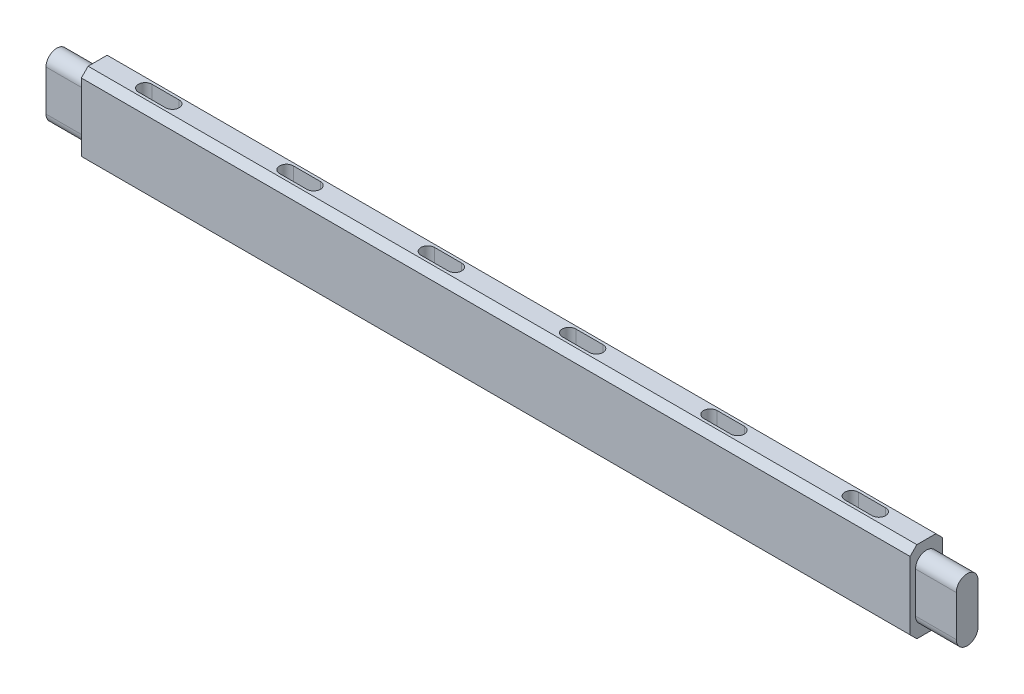
SolidWorks part; units mm, degrees
ref_plane "Front" through (0, 0, 0) normal (0, 0, 1) x (1, 0, 0)
ref_plane "Top" through (0, 0, 0) normal (0, 1, 0) x (1, 0, 0)
ref_plane "Right" through (0, 0, 0) normal (1, 0, 0) x (0, 0, -1)
sketch "Esquisse1" plane through (0, 0, 0) normal (0, 0, 1) x (1, 0, 0)
  line L1 (0, 0) -> (610, 0)
  line L2 (0, 0) -> (0, 60)
  line L3 (0, 60) -> (610, 60)
  line L4 (610, 0) -> (610, 60)
  dimension "D1" = 610
  dimension "D2" = 60
extrude "Boss.-Extru.1" add sketch "Esquisse1" along normal blind 24
sketch "Esquisse2" plane through (0, 0, 0) normal (-1, 0, 0) x (0, 0, 1)
  line L0 (12, 0) -> (12, 60) construction
  line L1 (24, 0) -> (0, 0) construction
  line L2 (24, 60) -> (0, 60) construction
  line L3 (12, 15) -> (12, 45) construction
  line L4 (4, 15) -> (4, 45)
  line L5 (20, 15) -> (20, 45)
  arc A0 (4, 15) -> (20, 15) centre (12, 15) ccw
  arc A1 (20, 45) -> (4, 45) centre (12, 45) ccw
  point P8 (12, 30)
  dimension "D1" = 16
  dimension "D2" = 30
extrude "Boss.-Extru.2" add sketch "Esquisse2" along normal blind 30
extrude "Boss.-Extru.3" add sketch "Esquisse2<2>" against normal blind 30 from vertex starting at point (610, 60, 0)
sketch "Esquisse2<2>" plane through (0, 0, 0) normal (-1, 0, 0) x (0, 0, 1) same geometry as "Esquisse2"
chamfer "Chanfrein1" distance 5 angle 45 4 edges at (305, 0, 24) (305, 0, 0) (305, 60, 0) (305, 60, 24)
sketch "Esquisse3" [suppressed] plane through (0, 80, 0) normal (0, 1, 0) x (1, 0, 0)
  line L0 (305, -27) -> (305, -5) construction
  line L1 (0, -27) -> (610, -27) construction
  line L2 (305, -16) -> (415, -16) construction
  line L3 (360, -16) -> (360, -5) construction
  line L4 (610, -5) -> (0, -5) construction
  line L7 (305, -16) -> (195, -16) construction
  line L8 (185, -16) -> (205, -16) construction
  line L9 (185, -11) -> (205, -11)
  line L10 (185, -21) -> (205, -21)
  line L11 (82, -16) -> (102, -16) construction
  line L12 (82, -11) -> (102, -11)
  line L13 (82, -21) -> (102, -21)
  line L14 (-21, -16) -> (-1, -16) construction
  line L15 (-21, -11) -> (-1, -11)
  line L16 (-21, -21) -> (-1, -21)
  line L17 (-124, -16) -> (-104, -16) construction
  line L18 (-124, -11) -> (-104, -11)
  line L19 (-124, -21) -> (-104, -21)
  line L20 (-227, -16) -> (-207, -16) construction
  line L21 (-227, -11) -> (-207, -11)
  line L22 (-227, -21) -> (-207, -21)
  line L23 (595, -16) -> (315, -16) construction
  line L24 (595, -16) -> (315, -16) construction
  line L25 (295, -16) -> (315, -16) construction
  line L26 (295, -11) -> (315, -11)
  line L27 (295, -21) -> (315, -21)
  line L29 (837, -16) -> (817, -16) construction
  line L30 (837, -11) -> (817, -11)
  line L31 (837, -21) -> (817, -21)
  line L32 (734, -16) -> (714, -16) construction
  line L33 (734, -11) -> (714, -11)
  line L34 (734, -21) -> (714, -21)
  line L35 (631, -16) -> (611, -16) construction
  line L36 (631, -11) -> (611, -11)
  line L37 (631, -21) -> (611, -21)
  line L38 (528, -16) -> (508, -16) construction
  line L39 (528, -11) -> (508, -11)
  line L40 (528, -21) -> (508, -21)
  line L41 (425, -16) -> (405, -16) construction
  line L42 (425, -11) -> (405, -11)
  line L43 (425, -21) -> (405, -21)
  line L89 (-65, -16) -> (-45, -16) construction
  line L90 (-65, -11) -> (-45, -11)
  line L91 (-65, -21) -> (-45, -21)
  line L92 (-330, -16) -> (-310, -16) construction
  line L93 (-330, -11) -> (-310, -11)
  line L94 (-330, -21) -> (-310, -21)
  arc A0 (185, -11) -> (185, -21) centre (185, -16) ccw
  arc A1 (205, -21) -> (205, -11) centre (205, -16) ccw
  arc A2 (82, -11) -> (82, -21) centre (82, -16) ccw
  arc A3 (102, -21) -> (102, -11) centre (102, -16) ccw
  arc A4 (-21, -11) -> (-21, -21) centre (-21, -16) ccw
  arc A5 (-1, -21) -> (-1, -11) centre (-1, -16) ccw
  arc A6 (-124, -11) -> (-124, -21) centre (-124, -16) ccw
  arc A7 (-104, -21) -> (-104, -11) centre (-104, -16) ccw
  arc A8 (-227, -11) -> (-227, -21) centre (-227, -16) ccw
  arc A9 (-207, -21) -> (-207, -11) centre (-207, -16) ccw
  arc A10 (295, -11) -> (295, -21) centre (295, -16) ccw
  arc A11 (315, -21) -> (315, -11) centre (315, -16) ccw
  arc A14 (837, -11) -> (837, -21) centre (837, -16) cw
  arc A15 (817, -21) -> (817, -11) centre (817, -16) cw
  arc A16 (734, -11) -> (734, -21) centre (734, -16) cw
  arc A17 (714, -21) -> (714, -11) centre (714, -16) cw
  arc A18 (631, -11) -> (631, -21) centre (631, -16) cw
  arc A19 (611, -21) -> (611, -11) centre (611, -16) cw
  arc A20 (528, -11) -> (528, -21) centre (528, -16) cw
  arc A21 (508, -21) -> (508, -11) centre (508, -16) cw
  arc A22 (425, -11) -> (425, -21) centre (425, -16) cw
  arc A23 (405, -21) -> (405, -11) centre (405, -16) cw
  arc A56 (-330, -11) -> (-330, -21) centre (-330, -16) ccw
  arc A57 (-310, -21) -> (-310, -11) centre (-310, -16) ccw
  point P10 (195, -16)
  point P19 (92, -16)
  point P26 (-11, -16)
  point P33 (-114, -16)
  point P40 (-217, -16)
  point P49 (305, -16)
  point P59 (827, -16)
  point P66 (724, -16)
  point P73 (621, -16)
  point P80 (518, -16)
  point P87 (415, -16)
  point P94 (-11, -16)
  point P104 (-11, -16)
  point P111 (-11, -16)
  point P118 (-11, -16)
  point P125 (-16, -16)
  point P132 (-16, -16)
  point P139 (-16, -16)
  point P146 (-16, -16)
  point P153 (-55, -16)
  point P160 (-55, -16)
  point P167 (-55, -16)
  point P174 (-55, -16)
  point P181 (-55, -16)
  point P188 (-55, -16)
  point P195 (-55, -16)
  point P202 (-55, -16)
  point P209 (-320, -16)
  dimension "D1" = 10
  dimension "D2" = 208
  dimension "D3" = 20
  dimension "D4" = 6
  dimension "D5" = 104
extrude "Enlèv. mat.-Extru.1" [suppressed] cut sketch "Esquisse3" against normal blind 15
sketch "Esquisse5" plane through (0, 60, 0) normal (0, 1, 0) x (1, 0, 0)
  line L0 (253, -27.4919) -> (253, 3.4919) construction
  line L1 (0, 0) -> (610, 0) construction
  line L2 (253, -12) -> (357, -12) construction
  line L3 (305, -12) -> (305, -5) construction
  line L5 (610, -5) -> (0, -5) construction
  line L7 (253, -12) -> (149, -12) construction
  line L8 (139, -12) -> (159, -12) construction
  line L9 (139, -7) -> (159, -7)
  line L10 (139, -17) -> (159, -17)
  line L11 (35, -12) -> (55, -12) construction
  line L12 (35, -7) -> (55, -7)
  line L13 (35, -17) -> (55, -17)
  line L23 (389.8909, -12) -> (263, -12) construction
  line L24 (389.8909, -12) -> (263, -12) construction
  line L25 (243, -12) -> (263, -12) construction
  line L26 (243, -7) -> (263, -7)
  line L27 (243, -17) -> (263, -17)
  line L35 (575, -12) -> (555, -12) construction
  line L36 (575, -7) -> (555, -7)
  line L37 (575, -17) -> (555, -17)
  line L38 (471, -12) -> (451, -12) construction
  line L39 (471, -7) -> (451, -7)
  line L40 (471, -17) -> (451, -17)
  line L41 (367, -12) -> (347, -12) construction
  line L42 (367, -7) -> (347, -7)
  line L43 (367, -17) -> (347, -17)
  line L341 (-69, -12) -> (-49, -12) construction
  line L342 (-69, -7) -> (-49, -7)
  line L343 (-69, -17) -> (-49, -17)
  line L344 (-173, -12) -> (-153, -12) construction
  line L345 (-173, -7) -> (-153, -7)
  line L346 (-173, -17) -> (-153, -17)
  line L347 (-277, -12) -> (-257, -12) construction
  line L348 (-277, -7) -> (-257, -7)
  line L349 (-277, -17) -> (-257, -17)
  line L350 (-381, -12) -> (-361, -12) construction
  line L351 (-381, -7) -> (-361, -7)
  line L352 (-381, -17) -> (-361, -17)
  line L353 (-69, -12) -> (-49, -12) construction
  line L354 (-69, -7) -> (-49, -7)
  line L355 (-69, -17) -> (-49, -17)
  line L356 (-173, -12) -> (-153, -12) construction
  line L357 (-173, -7) -> (-153, -7)
  line L358 (-173, -17) -> (-153, -17)
  line L359 (-277, -12) -> (-257, -12) construction
  line L360 (-277, -7) -> (-257, -7)
  line L361 (-277, -17) -> (-257, -17)
  line L362 (-381, -12) -> (-361, -12) construction
  line L363 (-381, -7) -> (-361, -7)
  line L364 (-381, -17) -> (-361, -17)
  arc A0 (139, -7) -> (139, -17) centre (139, -12) ccw
  arc A1 (159, -17) -> (159, -7) centre (159, -12) ccw
  arc A2 (35, -7) -> (35, -17) centre (35, -12) ccw
  arc A3 (55, -17) -> (55, -7) centre (55, -12) ccw
  arc A10 (243, -7) -> (243, -17) centre (243, -12) ccw
  arc A11 (263, -17) -> (263, -7) centre (263, -12) ccw
  arc A18 (575, -7) -> (575, -17) centre (575, -12) cw
  arc A19 (555, -17) -> (555, -7) centre (555, -12) cw
  arc A20 (471, -7) -> (471, -17) centre (471, -12) cw
  arc A21 (451, -17) -> (451, -7) centre (451, -12) cw
  arc A22 (367, -7) -> (367, -17) centre (367, -12) cw
  arc A23 (347, -17) -> (347, -7) centre (347, -12) cw
  arc A230 (-69, -7) -> (-69, -17) centre (-69, -12) ccw
  arc A231 (-49, -17) -> (-49, -7) centre (-49, -12) ccw
  arc A232 (-173, -7) -> (-173, -17) centre (-173, -12) ccw
  arc A233 (-153, -17) -> (-153, -7) centre (-153, -12) ccw
  arc A234 (-277, -7) -> (-277, -17) centre (-277, -12) ccw
  arc A235 (-257, -17) -> (-257, -7) centre (-257, -12) ccw
  arc A236 (-381, -7) -> (-381, -17) centre (-381, -12) ccw
  arc A237 (-361, -17) -> (-361, -7) centre (-361, -12) ccw
  point P4 (0, 0)
  point P10 (149, -12)
  point P18 (389.8909, -16.4919)
  point P19 (45, -12)
  point P24 (0, 0)
  point P25 (0, 0)
  point P26 (-169, -16.4919)
  point P29 (550.0258, -12)
  point P33 (-272, -16.4919)
  point P49 (253, -12)
  point P55 (-66, -16.4919)
  point P73 (565, -12)
  point P80 (461, -12)
  point P87 (357, -12)
  point P94 (-225.2423, -16.4919)
  point P104 (-225.2423, -16.4919)
  point P111 (-225.2423, -16.4919)
  point P118 (-225.2423, -16.4919)
  point P125 (-230.2423, -16.4919)
  point P132 (-230.2423, -16.4919)
  point P139 (-230.2423, -16.4919)
  point P146 (-230.2423, -16.4919)
  point P153 (-269.2423, -16.4919)
  point P160 (-269.2423, -16.4919)
  point P167 (-269.2423, -16.4919)
  point P174 (-269.2423, -16.4919)
  point P181 (-269.2423, -16.4919)
  point P188 (-269.2423, -16.4919)
  point P195 (-269.2423, -16.4919)
  point P202 (-269.2423, -16.4919)
  point P209 (-534.2423, -16.4919)
  point P216 (-534.2423, -16.4919)
  point P223 (-375, -16.4919)
  point P230 (-66, -16.4919)
  point P237 (-169, -16.4919)
  point P244 (-272, -16.4919)
  point P251 (-375, -16.4919)
  point P258 (-66, -16.4919)
  point P265 (-169, -16.4919)
  point P272 (-272, -16.4919)
  point P279 (-375, -16.4919)
  point P286 (-66, -16.4919)
  point P293 (-169, -16.4919)
  point P300 (-272, -16.4919)
  point P307 (-375, -16.4919)
  point P314 (-66, -16.4919)
  point P321 (-169, -16.4919)
  point P328 (-272, -16.4919)
  point P335 (-375, -16.4919)
  point P342 (-66, -16.4919)
  point P349 (-169, -16.4919)
  point P356 (-272, -16.4919)
  point P363 (-375, -16.4919)
  point P370 (-66, -16.4919)
  point P377 (-169, -16.4919)
  point P384 (-272, -16.4919)
  point P391 (-375, -16.4919)
  point P398 (-66, -16.4919)
  point P405 (-169, -16.4919)
  point P412 (-272, -16.4919)
  point P419 (-375, -16.4919)
  point P426 (-66, -16.4919)
  point P433 (-169, -16.4919)
  point P440 (-272, -16.4919)
  point P447 (-375, -16.4919)
  point P454 (-66, -16.4919)
  point P461 (-169, -16.4919)
  point P468 (-272, -16.4919)
  point P475 (-375, -16.4919)
  point P482 (-55.5, -16.4919)
  point P489 (-158.5, -16.4919)
  point P496 (-261.5, -16.4919)
  point P503 (-364.5, -16.4919)
  point P510 (-55.5, -16.4919)
  point P517 (-158.5, -16.4919)
  point P524 (-261.5, -16.4919)
  point P531 (-364.5, -16.4919)
  point P538 (-57, -16.4919)
  point P545 (-160, -16.4919)
  point P552 (-263, -16.4919)
  point P559 (-366, -16.4919)
  point P566 (-57, -16.4919)
  point P573 (-160, -16.4919)
  point P580 (-263, -16.4919)
  point P587 (-366, -16.4919)
  point P594 (-59, -16.4919)
  point P601 (-163, -16.4919)
  point P608 (-267, -16.4919)
  point P615 (-371, -16.4919)
  point P622 (-59, -16.4919)
  point P629 (-163, -16.4919)
  point P636 (-267, -16.4919)
  point P643 (-371, -16.4919)
  point P650 (-59, -16.4919)
  point P657 (-163, -16.4919)
  point P664 (-267, -16.4919)
  point P671 (-371, -16.4919)
  point P678 (-59, -16.4919)
  point P685 (-163, -16.4919)
  point P692 (-267, -16.4919)
  point P699 (-371, -16.4919)
  point P706 (-59, -12)
  point P713 (-163, -12)
  point P720 (-267, -12)
  point P727 (-371, -12)
  point P734 (-59, -12)
  point P741 (-163, -12)
  point P748 (-267, -12)
  point P755 (-371, -12)
  point P762 (-59, -12)
  point P769 (-163, -12)
  point P776 (-267, -12)
  point P783 (-371, -12)
  point P790 (-59, -12)
  point P797 (-163, -12)
  point P804 (-267, -12)
  point P811 (-371, -12)
  point P818 (-59, -12)
  point P825 (-163, -12)
  point P832 (-267, -12)
  point P839 (-371, -12)
  dimension "D1" = 10
  dimension "D2" = 208
  dimension "D3" = 20
  dimension "D4" = 6
  dimension "D5" = 104
  dimension "D6" = 12
  dimension "D7" = 104
extrude "Enlèv. mat.-Extru.2" cut sketch "Esquisse5" against normal blind 15
